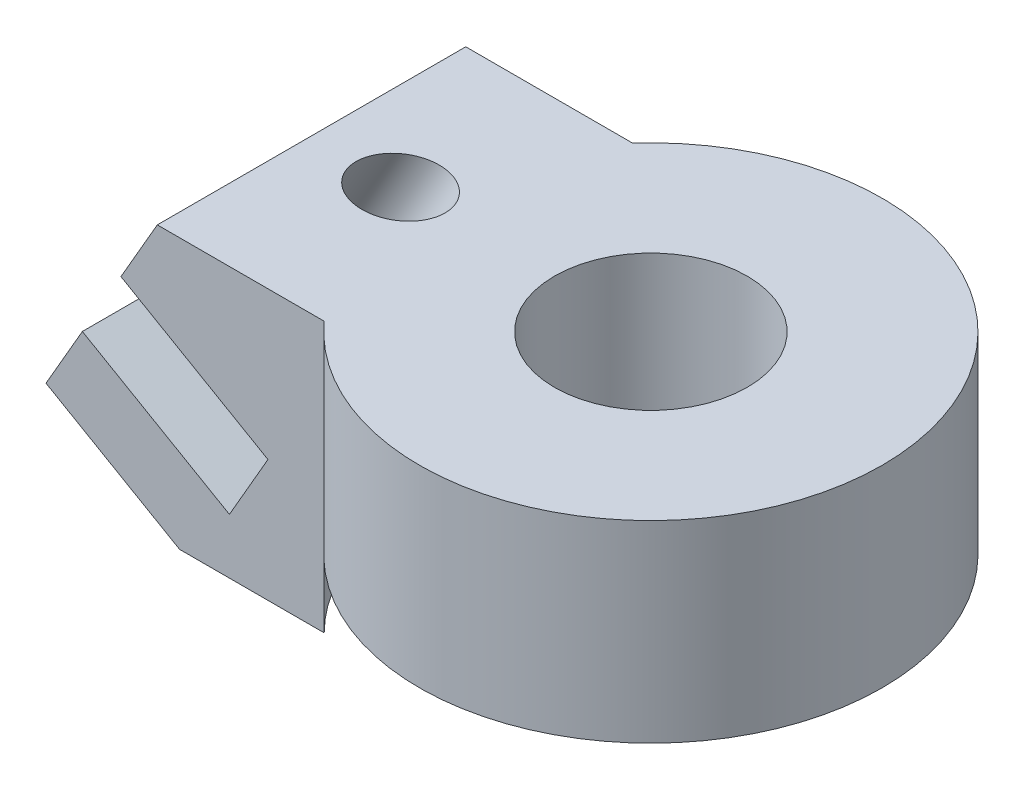
SolidWorks part; units mm, degrees
ref_plane "前视基准面" through (0, 0, 0) normal (0, 0, 1) x (1, 0, 0)
ref_plane "上视基准面" through (0, 0, 0) normal (0, 1, 0) x (1, 0, 0)
ref_plane "右视基准面" through (0, 0, 0) normal (1, 0, 0) x (0, 0, -1)
sketch "草图2" plane through (0, 0, 0) normal (0, 1, 0) x (1, 0, 0)
  circle A0 centre (0, 0) radius 6
extrude "凸台-拉伸1" add sketch "草图2" along normal blind 5
sketch "草图3" plane through (0, 5, 0) normal (0, 1, 0) x (1, 0, 0)
  circle A0 centre (0, 0) radius 2.5
extrude "切除-拉伸1" cut sketch "草图3" against normal up to surface (5 mm away) up to face at (0, 0, 6)
sketch "草图4" plane through (0, 0, 0) normal (0, 0, 1) x (1, 0, 0)
  line L0 (0, 0) -> (-3.0701, 0) construction
  line L1 (-3.0701, 0) -> (-11.6873, 0)
  line L2 (-3.0701, 0) -> (-3.0701, 5)
  line L3 (-3.0701, 5) -> (-11.6873, 5)
  line L4 (-11.6873, 0) -> (-11.6873, 5)
extrude "凸台-拉伸2" add sketch "草图4" along normal blind 4 and the other way blind 4
ref_plane "基准面4" through (-8.7655, 5.0608, 0) normal (0.866, -0.5, 0) x (0, 0, 1)
sketch "草图5" plane through (-8.7655, 5.0608, 0) normal (0.866, -0.5, 0) x (0, 0, 1)
  line L1 (-7.6932, 0) -> (9.9976, 0)
  line L2 (-7.6932, 0) -> (-7.6932, 8.2589)
  line L3 (-7.6932, 8.2589) -> (9.9976, 8.2589)
  line L4 (9.9976, 0) -> (9.9976, 8.2589)
extrude "切除-拉伸3" cut sketch "草图5" against normal blind 4.5
ref_plane "基准面5" through (-0.0351, -0.0608, 0) normal (0.5, 0.866, 0) x (0, 0, 1)
ref_plane "基准面8" through (0, 2.5, 0) normal (0, 1, 0) x (1, 0, 0)
ref_axis "基准轴3" through (-10.2439, 2.5, -6.6) along (0, 0, 1)
ref_plane "基准面9" through (-1.4785, -2.5608, 0) normal (0.5, 0.866, 0) x (0.866, -0.5, 0)
sketch "草图12" plane through (0, 0, 0) normal (0, -1, 0) x (1, 0, 0)
  line L0 (-11.6873, 4) -> (-4.4721, 4) construction
  line L1 (-11.6873, -4) -> (-11.6873, 4) construction
  line L2 (-11.6873, -4) -> (-4.4721, -4) construction
  line L3 (-11.6873, 4) -> (-4.4721, 4)
  line L4 (-11.6873, -4) -> (-11.6873, 4)
  line L5 (-11.6873, -4) -> (-4.4721, -4)
  arc A2 (-4.4721, -4) -> (-4.4721, 4) centre (-0.4721, 0) cw
extrude "凸台-拉伸5" add sketch "草图12" along normal blind 2
sketch "草图10" plane through (-1.4785, -2.5608, 0) normal (0.5, 0.866, 0) x (0.866, -0.5, 0)
  line L0 (-10.1215, -4) -> (3.873, -4) construction
  line L1 (-10.1215, 4) -> (-10.1215, -4) construction
  line L2 (-10.1215, 4) -> (-3.873, 4) construction
  line L3 (-10.1215, -4) -> (-5.7181, -4)
  line L4 (-10.1215, 4) -> (-10.1215, -4)
  line L5 (-10.1215, 4) -> (-5.7181, 4)
  line L6 (-5.7181, 4) -> (-5.7181, -4)
extrude "切除-拉伸7" cut sketch "草图10" against normal blind 1 and the other way blind 1
ref_plane "基准面13" through (-2.9218, -5.0608, 0) normal (0.5, 0.866, 0) x (0.866, -0.5, 0)
sketch "草图14" plane through (-2.9218, -5.0608, 0) normal (0.5, 0.866, 0) x (0.866, -0.5, 0)
  line L0 (-9.1215, 4) -> (-2.873, 4) construction
  line L1 (-2.873, -4) -> (-9.1215, -4) construction
  line L2 (-10.1215, -4) -> (-10.1215, 4) construction
  line L3 (-10.1215, 4) -> (-9.1215, 4) construction
  line L4 (-9.1215, -4) -> (-10.1215, -4) construction
  line L5 (-9.1215, 4) -> (-5.5359, 4)
  line L6 (-5.5359, -4) -> (-9.1215, -4)
  line L7 (-10.1215, -4) -> (-10.1215, 4)
  line L8 (-10.1215, 4) -> (-9.1215, 4)
  line L9 (-9.1215, -4) -> (-10.1215, -4)
  line L10 (-5.5359, 4) -> (-5.5359, -4)
extrude "切除-拉伸8" cut sketch "草图14" against normal blind 4
sketch "草图15" plane through (-2.9218, -5.0608, 0) normal (-0.5, -0.866, 0) x (0.866, -0.5, 0)
  line L0 (-10.1215, 0) -> (-6.1215, 0) construction
  line L1 (-10.1215, -4) -> (-10.1215, 4) construction
  line L2 (-6.1215, -4) -> (-6.1215, 4) construction
  circle A0 centre (-8.1215, 0) radius 1
extrude "切除-拉伸9" cut sketch "草图15" against normal blind 8
ref_plane "基准面12" through (-0.7568, -1.3108, 0) normal (0.5, 0.866, 0) x (0.866, -0.5, 0)
